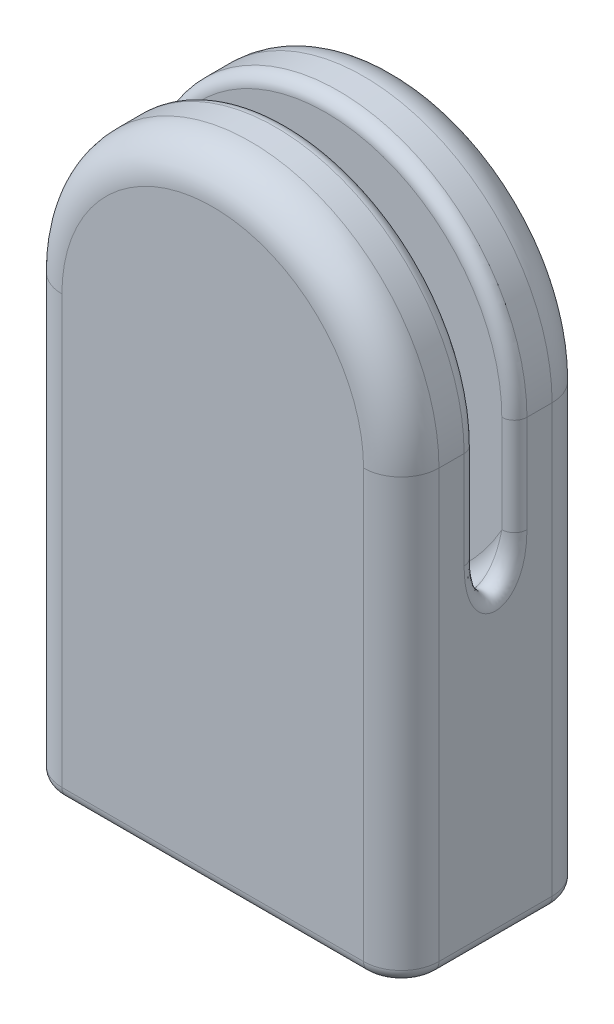
SolidWorks part; units mm, degrees
material "PVC Rigid"
ref_plane "Front Plane" through (0, 0, 0) normal (0, 0, 1) x (1, 0, 0)
ref_plane "Top Plane" through (0, 0, 0) normal (0, 1, 0) x (1, 0, 0)
ref_plane "Right Plane" through (0, 0, 0) normal (1, 0, 0) x (0, 0, -1)
sketch "Sketch1" plane through (0, 0, 0) normal (0, 1, 0) x (1, 0, 0)
  line L1 (-38.1, 19.05) -> (38.1, 19.05)
  line L2 (-38.1, 19.05) -> (-38.1, -19.05)
  line L3 (-38.1, -19.05) -> (38.1, -19.05)
  line L4 (38.1, 19.05) -> (38.1, -19.05)
  point P4 (0, 19.05)
  point P6 (-38.1, 0)
  dimension "D1" = 38.1
  dimension "D2" = 76.2
extrude "Boss-Extrude1" add sketch "Sketch1" along normal blind 127
sketch "Sketch2" plane through (0, 0, 19.05) normal (0, 0, 1) x (1, 0, 0)
  line L2 (-38.1, 127) -> (38.1, 127) construction
  line L5 (-38.1, 127) -> (-38.1, 0) construction
  line L6 (-38.1, 127) -> (38.1, 127) construction
  line L7 (-38.1, 127) -> (38.1, 127)
  line L8 (38.1, 127) -> (38.1, 0) construction
  arc A0 (-38.1, 88.9) -> (38.1, 88.9) centre (0, 88.9) cw
extrude "Cut-Extrude1" cut sketch "Sketch2" against normal through all
fillet "Fillet2" radius 2.54 4 edges at (0, 0, -19.05) (-38.1, 0, 0) (0, 0, 19.05) (38.1, 0, 0)
fillet "Fillet3" radius 7.62 10 edges at (-37.3561, 0.7439, 18.3061) (37.3561, 0.7439, 18.3061) (-37.3561, 0.7439, -18.3061) (37.3561, 0.7439, -18.3061) (38.1, 45.72, -19.05) (-38.1, 45.72, -19.05) (38.1, 45.72, 19.05) (-38.1, 45.72, 19.05) (0, 127, -19.05) (0, 127, 19.05)
sketch "Sketch4" plane through (0, 0, 0) normal (1, 0, 0) x (0, 0, -1)
  line L0 (-19.4008, 88.9) -> (19.4008, 88.9) construction
  line L1 (-3.81, 48.26) -> (-3.81, 88.9)
  line L2 (3.81, 48.26) -> (3.81, 88.9)
  line L3 (11.43, 127) -> (-11.43, 127) construction
  line L4 (3.81, 88.9) -> (-3.81, 88.9)
  arc A0 (-3.81, 48.26) -> (3.81, 48.26) centre (0, 48.26) ccw
  point P6 (0, 88.9)
  dimension "D3" = 40.64
  dimension "D1" = 7.62
  dimension "D2" = 38.1
revolve "Cut-Revolve1" cut sketch "Sketch4" angle 360 about L0
fillet "Fillet5" radius 2.54 8 edges at (38.1, 111.793, 0.0944) (38.1, 81.8289, -3.81) (0, 127, -3.81) (-38.1, 81.8289, -3.81) (-38.1, 111.793, -0.0944) (-38.1, 81.8289, 3.81) (0, 127, 3.81) (38.1, 81.8289, 3.81)
sketch "Sketch5" plane through (0, 0, 0) normal (0, 0, 1) x (1, 0, 0)
  circle A0 centre (0, 88.9) radius 3.175
  arc A2 (38.1, 88.9) -> (-38.1, 88.9) centre (0, 88.9) ccw construction
  dimension "D1" = 6.35
extrude "Cut-Extrude2" cut sketch "Sketch5" against normal blind 12.7 and the other way blind 12.7
